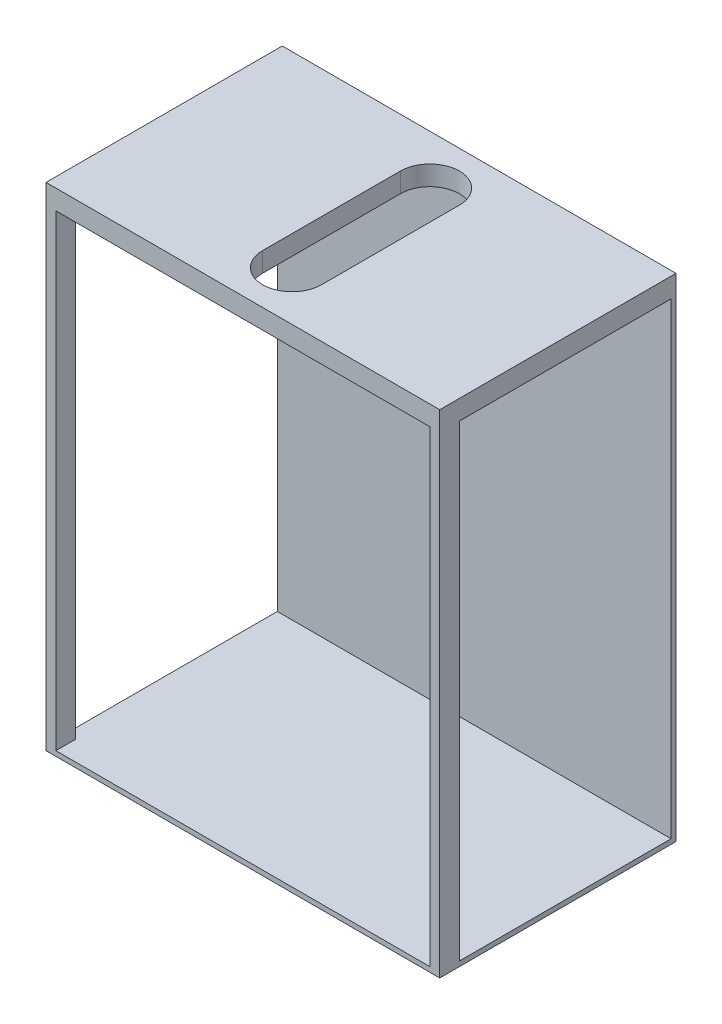
SolidWorks part; units mm, degrees
ref_plane "Front Plane" through (0, 0, 0) normal (0, 0, 1) x (1, 0, 0)
ref_plane "Top Plane" through (0, 0, 0) normal (0, 1, 0) x (1, 0, 0)
ref_plane "Right Plane" through (0, 0, 0) normal (1, 0, 0) x (0, 0, -1)
sketch "Sketch1" plane through (0, 0, 0) normal (0, 0, 1) x (1, 0, 0)
  line L1 (0, 0) -> (508, 0)
  line L2 (0, 0) -> (0, 635)
  line L3 (0, 635) -> (508, 635)
  line L4 (508, 0) -> (508, 635)
  dimension "D1" = 635
  dimension "D2" = 508
extrude "Boss-Extrude1" add sketch "Sketch1" along normal blind 6.35
sketch "Sketch3" plane through (0, 0, 0) normal (0, 1, 0) x (1, 0, 0)
  line L1 (0, -6.35) -> (508, -6.35)
  line L2 (0, -6.35) -> (0, -304.8)
  line L3 (0, -304.8) -> (508, -304.8)
  line L4 (508, -6.35) -> (508, -304.8)
  point P5 (0, 0)
  dimension "D1" = 298.45
extrude "Boss-Extrude3" add sketch "Sketch3" along normal blind 6.35
sketch "Sketch4" plane through (0, 0, 0) normal (1, 0, 0) x (0, 0, -1)
  line L0 (-304.8, 6.35) -> (-304.8, 635)
  line L1 (-304.8, 635) -> (-6.35, 635)
  line L2 (-6.35, 635) -> (-6.35, 609.6)
  line L4 (-304.8, 6.35) -> (-6.35, 6.35) construction
  line L6 (-6.35, 609.6) -> (-279.4, 609.6)
  line L7 (-6.35, 635) -> (-6.35, 6.35) construction
  line L8 (-279.4, 609.6) -> (-279.4, 6.35)
  line L9 (-279.4, 6.35) -> (-304.8, 6.35)
  dimension "D1" = 25.4
  dimension "D2" = 25.4
extrude "Boss-Extrude4" add sketch "Sketch4" along normal blind 12.7
sketch "Sketch5" plane through (0, 0, 0) normal (0, 0, 1) x (1, 0, 0)
  line L0 (254, 635) -> (254, 0) construction
  line L6 (0, 0) -> (508, 0) construction
  line L7 (508, 635) -> (0, 635) construction
  point P6 (254, 635)
  point P9 (254, 0)
ref_plane "Plane1" through (254, 0, 0) normal (1, 0, 0) x (0, 0, -1)
mirror "Mirror1" about plane through (254, 0, 0) normal (1, 0, 0) of "Boss-Extrude4"
ref_plane "Plane2" through (12.7, 0, 0) normal (1, 0, 0) x (0, 0, -1)
sketch "Sketch6" plane through (12.7, 0, 0) normal (1, 0, 0) x (0, 0, -1)
  line L1 (-304.8, 635) -> (-6.35, 635)
  line L2 (-304.8, 635) -> (-304.8, 609.6)
  line L3 (-304.8, 609.6) -> (-6.35, 609.6)
  line L4 (-6.35, 635) -> (-6.35, 609.6)
extrude "Boss-Extrude6" add sketch "Sketch6" along normal up to surface (482.6 mm away) up to face at (495.3, 416.9833, 196.85)
ref_plane "Plane3" through (0, 635, 0) normal (0, 1, 0) x (1, 0, 0)
sketch "Sketch7" plane through (0, 635, 0) normal (0, 1, 0) x (1, 0, 0)
  line L0 (508, 0) -> (0, 0) construction
  line L1 (254, 0) -> (254, -304.8) construction
  line L2 (508, -304.8) -> (0, -304.8) construction
  line L3 (0, -152.4) -> (508, -152.4) construction
  line L4 (0, -304.8) -> (0, 0) construction
  line L5 (508, -304.8) -> (508, 0) construction
  line L6 (254, -63.5) -> (254, -241.3) construction
  line L7 (292.1, -63.5) -> (292.1, -241.3)
  line L8 (215.9, -63.5) -> (215.9, -241.3)
  arc A1 (292.1, -63.5) -> (215.9, -63.5) centre (254, -63.5) ccw
  arc A2 (215.9, -241.3) -> (292.1, -241.3) centre (254, -241.3) ccw
  point P15 (254, -152.4)
  dimension "D1" = 76.2
  dimension "D2" = 177.8
extrude "Cut-Extrude1" cut sketch "Sketch7" against normal up to surface (25.4 mm away) up to face at (254, 609.6, 217.4875)
